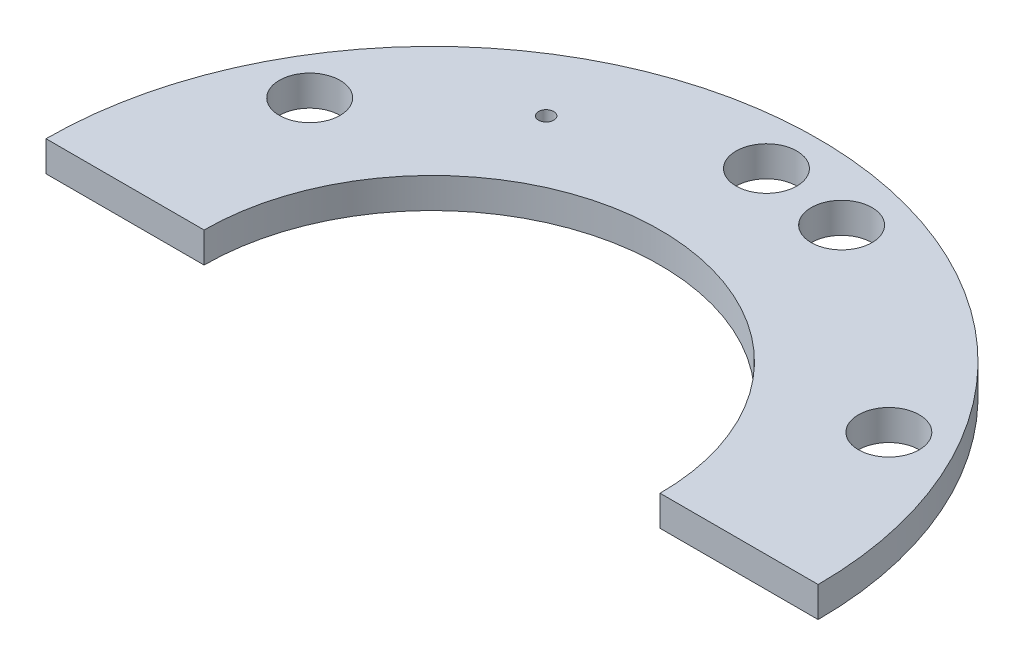
SolidWorks part; units mm, degrees
material "ABS"
ref_plane "Front Plane" through (0, 0, 0) normal (0, 0, 1) x (1, 0, 0)
ref_plane "Top Plane" through (0, 0, 0) normal (0, 1, 0) x (1, 0, 0)
ref_plane "Right Plane" through (0, 0, 0) normal (1, 0, 0) x (0, 0, -1)
sketch "Sketch1" plane through (0, 0, 0) normal (0, 1, 0) x (1, 0, 0)
  circle A0 centre (0, 0) radius 12.7
  dimension "D1" = 25.4
extrude "Boss-Extrude1" add sketch "Sketch1" along normal blind 1
sketch "Sketch19" plane through (0, 1, 0) normal (0, 1, 0) x (1, 0, 0)
  circle A0 centre (0, 11) radius 1
  circle A1 centre (9.5263, 5.5) radius 1
  circle A2 centre (9.5263, -5.5) radius 1
  circle A3 centre (0, -11) radius 1
  circle A4 centre (-9.5263, -5.5) radius 1
  circle A5 centre (-9.5263, 5.5) radius 1
  point P13 (0, 0)
  dimension "D1" = 2
  dimension "D2" = 11
  dimension "D3" = 6
extrude "Cut-Extrude1" cut sketch "Sketch19" against normal through all both and the other way through all
sketch "Sketch20" plane through (0, 1, 0) normal (0, 1, 0) x (1, 0, 0)
  circle A0 centre (0, 0) radius 7.5
  dimension "D1" = 15
extrude "Cut-Extrude2" cut sketch "Sketch20" against normal through all both and the other way through all
sketch "Sketch21" plane through (0, 0, 0) normal (0, 0, 1) x (1, 0, 0)
  line L1 (-36.7533, 32.3113) -> (29.1209, 32.3113)
  line L2 (-36.7533, 32.3113) -> (-36.7533, -19.668)
  line L3 (-36.7533, -19.668) -> (29.1209, -19.668)
  line L4 (29.1209, 32.3113) -> (29.1209, -19.668)
extrude "Cut-Extrude3" cut sketch "Sketch21" along normal through all
sketch "Sketch22" plane through (0, 1, 0) normal (0, 1, 0) x (1, 0, 0)
  line L0 (-9.5263, 5.5) -> (0, 11)
  line L1 (0, 0) -> (-5.125, 8.8768) construction
  circle A0 centre (-5.125, 8.8768) radius 0.25
  dimension "D1" = 0.5
  dimension "D2" = 10.25
extrude "Cut-Extrude4" cut sketch "Sketch22" against normal through all both and the other way through all contours A0 | A0 L1 | L1 A0 region at (-5.125, 1, -8.8768)
sketch "Sketch23" plane through (0, 1, 0) normal (0, 1, 0) x (1, 0, 0)
  line L0 (0, 0) -> (-5.125, 8.8768) construction
  line L1 (-5.125, 8.8768) -> (0, 0) construction
  line L2 (0, 0) -> (4.5783, 17.0863) construction
  circle A0 centre (2.847, 10.6252) radius 1
  dimension "D1" = 2
  dimension "D2" = 11
  dimension "D3" = 45
extrude "Cut-Extrude5" cut sketch "Sketch23" against normal through all both and the other way through all
